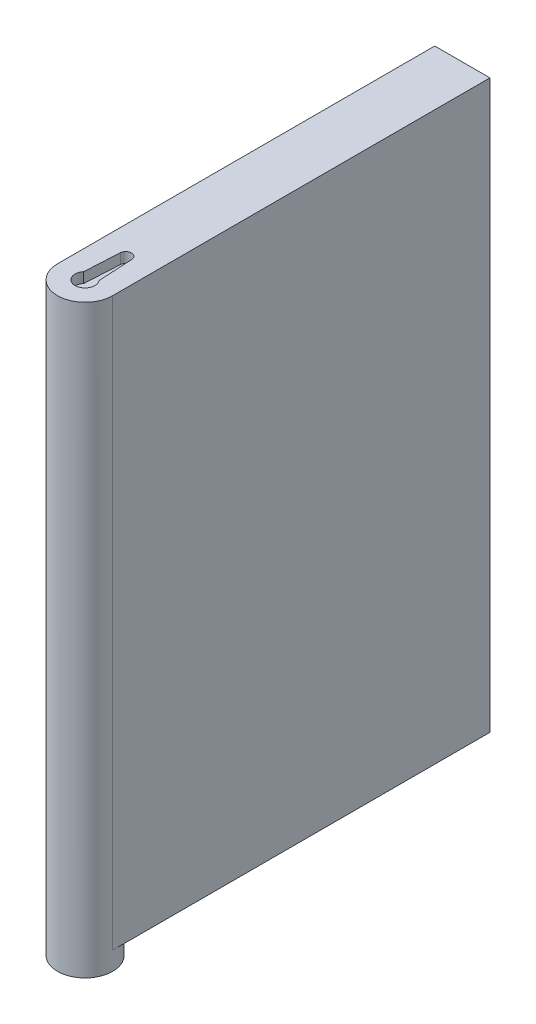
SolidWorks part; units mm, degrees
ref_plane "Front Plane" through (0, 0, 0) normal (0, 0, 1) x (1, 0, 0)
ref_plane "Top Plane" through (0, 0, 0) normal (0, 1, 0) x (1, 0, 0)
ref_plane "Right Plane" through (0, 0, 0) normal (1, 0, 0) x (0, 0, -1)
sketch "Sketch1" plane through (0, 0, 0) normal (0, 1, 0) x (1, 0, 0)
  line L1 (-9.525, -69.85) -> (9.525, -69.85)
  line L2 (-9.525, -69.85) -> (-9.525, 69.85)
  line L3 (-9.525, 69.85) -> (9.525, 69.85)
  line L4 (9.525, -69.85) -> (9.525, 69.85)
  line L5 (-9.525, -69.85) -> (9.525, 69.85) construction
  line L6 (-9.525, 69.85) -> (9.525, -69.85) construction
  arc A0 (-9.525, -60.325) -> (9.525, -60.325) centre (0, -60.325) ccw
  point P0 (0, 0)
  dimension "D1" = 139.7
  dimension "D2" = 19.05
extrude "Boss-Extrude1" add sketch "Sketch1" along normal mid plane 195.58 contours A0 L4 L3 L2 region at (0, 0, -1.0056)
sketch "Sketch2" plane through (0, -97.79, 0) normal (0, -1, 0) x (1, 0, 0)
  circle A0 centre (0, 60.325) radius 9.525
  dimension "D1" = 19.05
extrude "Boss-Extrude2" add sketch "Sketch2" along normal blind 6.35
sketch "Sketch3" plane through (0, 97.79, 0) normal (0, 1, 0) x (1, 0, 0)
  line L0 (-2.6531, -58.1379) -> (-1.9997, -46.1879) construction
  line L1 (1.9944, -46.1881) -> (2.6469, -58.1382) construction
  line L2 (-2.6531, -58.1379) -> (-1.9997, -46.1879)
  line L3 (1.9944, -46.1881) -> (2.6469, -58.1382)
  circle A0 centre (-0.0032, -60.3471) radius 3.45 construction
  arc A1 (1.9944, -46.1881) -> (-1.9997, -46.1879) centre (-0.0026, -46.2971) ccw construction
  arc A2 (-2.6531, -58.1379) -> (2.6469, -58.1382) centre (-0.0032, -60.3471) ccw
  arc A3 (1.9944, -46.1881) -> (-1.9997, -46.1879) centre (-0.0026, -46.2971) ccw
extrude "Cut-Extrude1" cut sketch "Sketch3" against normal blind 3.556
